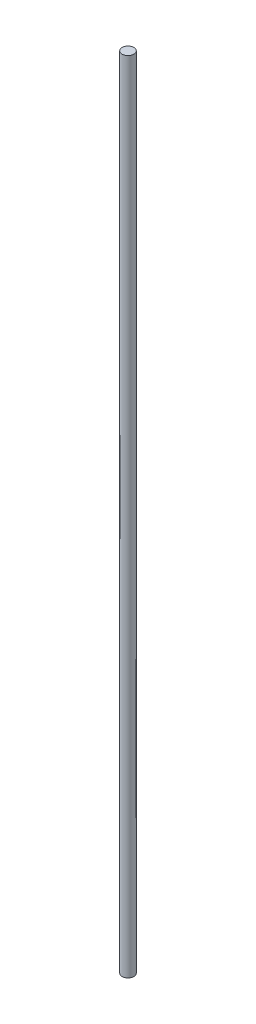
SolidWorks part; units mm, degrees
ref_plane "Front Plane" through (0, 0, 0) normal (0, 0, 1) x (1, 0, 0)
ref_plane "Top Plane" through (0, 0, 0) normal (0, 1, 0) x (1, 0, 0)
ref_plane "Right Plane" through (0, 0, 0) normal (1, 0, 0) x (0, 0, -1)
sketch "Sketch1" plane through (0, 0, 0) normal (0, 1, 0) x (1, 0, 0)
  circle A0 centre (0, 0) radius 6.35
  dimension "D1" = 12.7
extrude "Boss-Extrude1" add sketch "Sketch1" along normal mid plane 863.6
